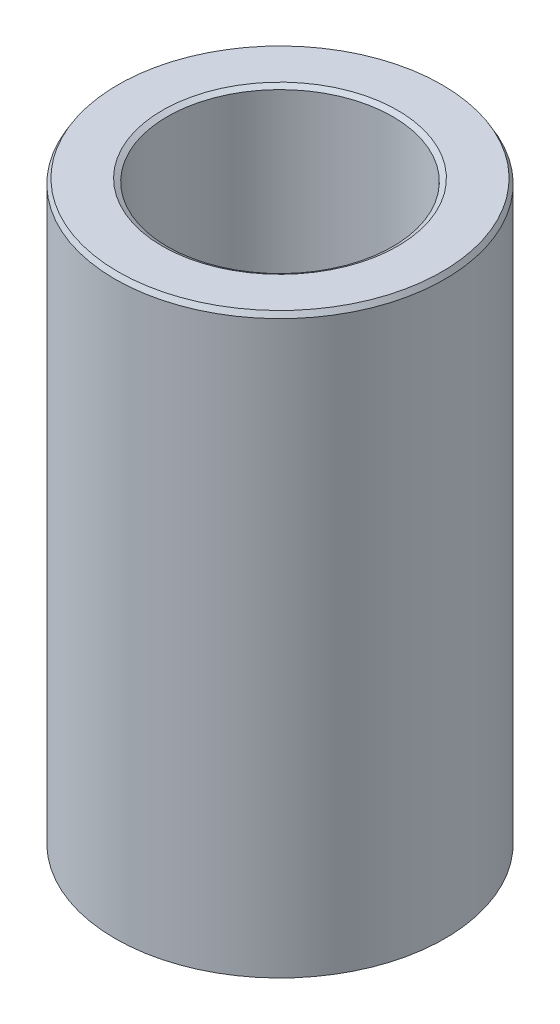
SolidWorks part; units mm, degrees
ref_plane "Front Plane" through (0, 0, 0) normal (0, 0, 1) x (1, 0, 0)
ref_plane "Top Plane" through (0, 0, 0) normal (0, 1, 0) x (1, 0, 0)
ref_plane "Right Plane" through (0, 0, 0) normal (1, 0, 0) x (0, 0, -1)
sketch "Sketch1" plane through (0, 0, 0) normal (0, 1, 0) x (1, 0, 0)
  circle A0 centre (0, 0) radius 15
  dimension "SLEEVE_OD" = 30
extrude "Boss-Extrude1" add sketch "Sketch1" along normal blind 52.6651
sketch "Sketch2" plane through (0, 0, 0) normal (0, 1, 0) x (1, 0, 0)
  circle A0 centre (0, 0) radius 10.2503
  dimension "BORE_D" = 20.5007
extrude "Cut-Extrude1" cut sketch "Sketch2" along normal through all
chamfer "Chamfer1" distance 0.4565 angle 30 4 edges at (0, 52.6651, 10.2503) (0, 0, 10.2503) (0, 0, 15) (0, 52.6651, 15) first distance on face at (0, 52.6651, 10.2503) first distance on face at (0, 0, 10.2503) first distance on face at (0, 52.6651, 15)
